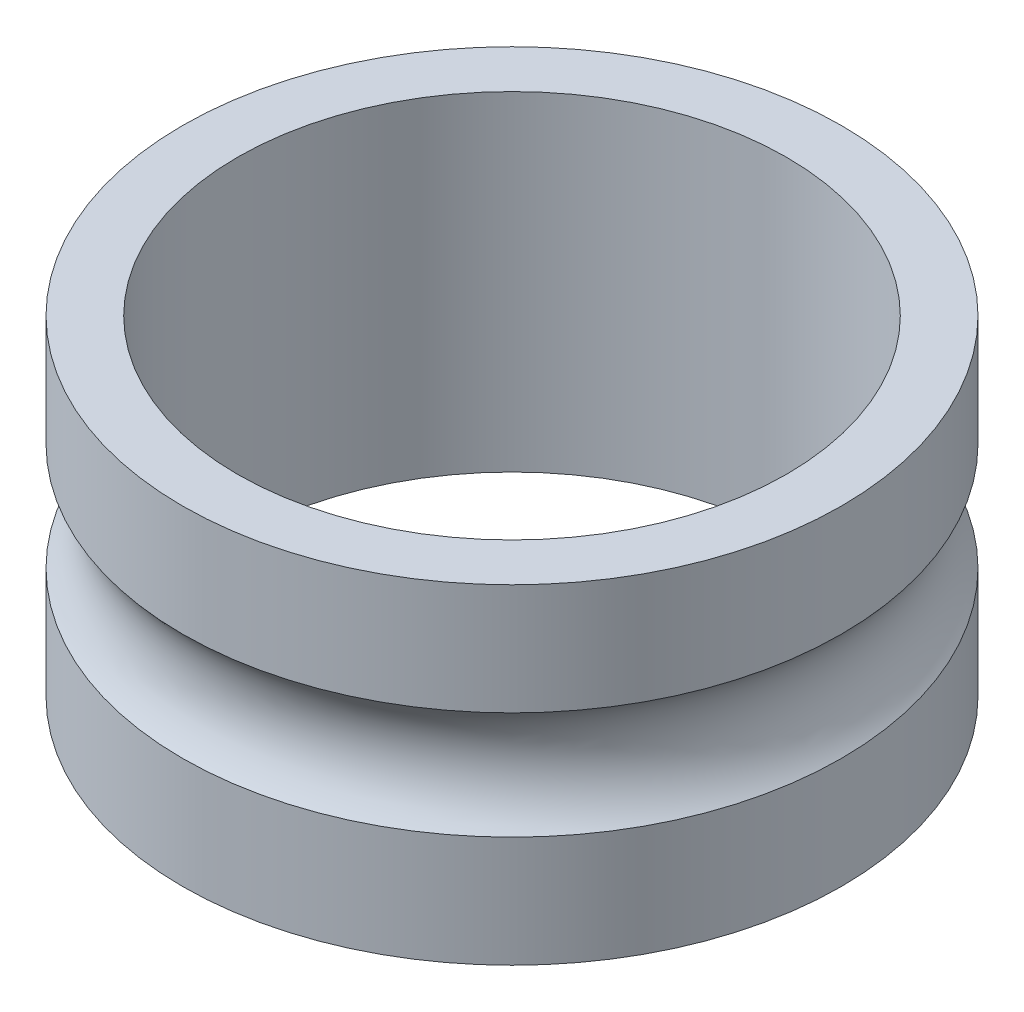
SolidWorks part; units mm, degrees
material "Chrome Stainless Steel"
ref_plane "Front Plane" through (0, 0, 0) normal (0, 0, 1) x (1, 0, 0)
ref_plane "Top Plane" through (0, 0, 0) normal (0, 1, 0) x (1, 0, 0)
ref_plane "Right Plane" through (0, 0, 0) normal (1, 0, 0) x (0, 0, -1)
sketch "DiaProfileS" plane through (0, 0, 0) normal (0, 1, 0) x (1, 0, 0)
  circle A0 centre (0, 0) radius 2.5
  circle A1 centre (0, 0) radius 3
  dimension "InnerDia" = 5
  dimension "Thickness" = 0.5
extrude "DiaProfile" add sketch "DiaProfileS" along normal mid plane 3
sketch "BearingPathProfileS" plane through (0, 0, 0) normal (0, 0, 1) x (1, 0, 0)
  line L0 (0, 0) -> (3.5, 0) construction
  line L3 (0, 1.5) -> (0, -1.5) construction
  circle A0 centre (3.5, 0) radius 0.7
  dimension "BallDia" = 1.4
  dimension "YDim" = 0.5
  dimension "RefRadius" = 3.5
revolve "BearingPathProfile" cut sketch "BearingPathProfileS" angle 360 about axis through (0, 1.5, 0) along (0, -1, 0)
